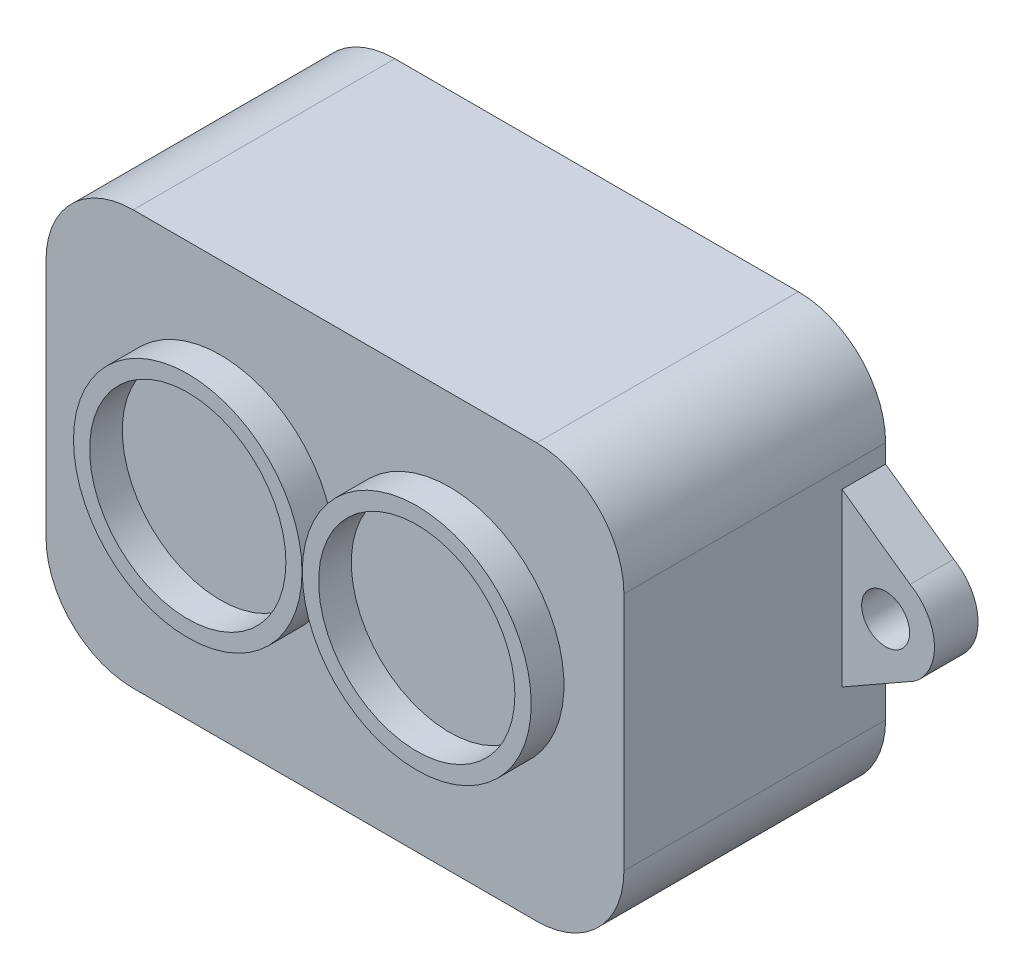
SolidWorks part; units mm, degrees
ref_plane "前视基准面" through (0, 0, 0) normal (0, 0, 1) x (1, 0, 0)
ref_plane "上视基准面" through (0, 0, 0) normal (0, 1, 0) x (1, 0, 0)
ref_plane "右视基准面" through (0, 0, 0) normal (1, 0, 0) x (0, 0, -1)
sketch "草图1" plane through (0, 0, 0) normal (0, 0, 1) x (1, 0, 0)
  line L1 (-13.25, -9.5) -> (13.25, -9.5)
  line L2 (-13.25, -9.5) -> (-13.25, 9.5)
  line L3 (-13.25, 9.5) -> (13.25, 9.5)
  line L4 (13.25, -9.5) -> (13.25, 9.5)
  line L5 (-13.25, -9.5) -> (13.25, 9.5) construction
  line L6 (-13.25, 9.5) -> (13.25, -9.5) construction
  point P0 (0, 0)
  dimension "D1" = 26.5
  dimension "D2" = 19
extrude "凸台-拉伸1" add sketch "草图1" along normal blind 12
sketch "草图2" plane through (0, 0, 12) normal (0, 0, 1) x (1, 0, 0)
  line L0 (0, 9.5) -> (0, 0.5)
  line L1 (13.25, 9.5) -> (-13.25, 9.5) construction
  line L2 (0, 0.5) -> (-5.25, 0.5)
  line L3 (0, 0.5) -> (5.25, 0.5)
  circle A0 centre (-5.25, 0.5) radius 5.25
  circle A1 centre (5.25, 0.5) radius 5.25
  circle A2 centre (-5.25, 0.5) radius 4.5
  circle A3 centre (5.25, 0.5) radius 4.5
  dimension "D3" = 5.25
  dimension "D1" = 9
  dimension "D2" = 5.25
extrude "凸台-拉伸6" add sketch "草图2" along normal blind 1.5
fillet "圆角1" radius 4 4 edges at (-13.25, 9.5, 6) (-13.25, -9.5, 6) (13.25, -9.5, 6) (13.25, 9.5, 6)
sketch "草图3" plane through (0, 0, 0) normal (0, 0, -1) x (-1, 0, 0)
  line L0 (0, 9.5) -> (0, 0.5)
  line L1 (-9.25, 9.5) -> (9.25, 9.5) construction
  line L2 (0, 0.5) -> (-15.25, 0.5)
  line L3 (-16.3734, 2.4375) -> (-16.5782, -1.3034)
  line L4 (-16.5782, -1.3034) -> (-13.25, -3.1974)
  line L5 (-13.25, -5.5) -> (-13.25, 5.5) construction
  line L6 (-16.3734, 2.4375) -> (-13.25, 4.6541)
  line L7 (-13.25, 4.6541) -> (-13.25, -3.1974)
  circle A0 centre (-15.25, 0.5) radius 1.1
  circle A1 centre (-15.25, 0.5) radius 2.2397
  dimension "D3" = 3.83
  dimension "D1" = 9
  dimension "D2" = 15.25
extrude "凸台-拉伸7" add sketch "草图3" against normal blind 2 separate body
mirror "镜向3" about plane through (0, 0, 0) normal (1, 0, 0) of "凸台-拉伸7"
sketch "草图4" plane through (0, 0, 12) normal (0, 0, 1) x (1, 0, 0)
  line L0 (0, 9.5) -> (0, 0.5)
  line L2 (9.25, 9.5) -> (-9.25, 9.5) construction
  line L3 (0, 0.5) -> (-5.25, 0.5)
  circle A0 centre (-5.25, 0.5) radius 5.24
  circle A1 centre (-5.25, 0.5) radius 4.5
  dimension "D1" = 9
  dimension "D2" = 5.25
extrude "凸台-拉伸11" add sketch "草图4" along normal blind 1.5
sketch "草图5" plane through (0, 0, 0) normal (0, 0, -1) x (-1, 0, 0)
  line L3 (9, -7.25) -> (-9, -7.25)
  line L4 (9, -7.25) -> (9, -11.75)
  line L5 (9, -11.75) -> (-9, -11.75)
  line L6 (-9, -7.25) -> (-9, -11.75)
  line L7 (9, -7.25) -> (-9, -11.75) construction
  line L8 (9, -11.75) -> (-9, -7.25) construction
  dimension "D1" = 18
  dimension "D2" = 4.5
extrude "凸台-拉伸12" add sketch "草图5" against normal blind 8.8
fillet "圆角2" radius 2 2 edges at (-9, -10.625, 8.8) (9, -10.625, 8.8)
fillet "圆角3" radius 1 2 edges at (9, -11.75, 3.4) (-9, -11.75, 3.4)
sketch "草图6" plane through (0, -11.75, 0) normal (0, -1, 0) x (1, 0, 0)
  line L0 (-5.25, 6.8) -> (-5.25, 0)
  line L1 (-5.25, 0) -> (5.25, 0)
  line L3 (8, 0) -> (-8, 0) construction
  line L6 (-5.25, 6.8) -> (5.25, 6.8)
  line L8 (5.25, 6.8) -> (5.25, 0)
  dimension "D1" = 10.5
extrude "切除-拉伸1" cut sketch "草图6" against normal blind 5
fillet "圆角4" radius 1 2 edges at (5.25, -9.25, 6.8) (-5.25, -9.25, 6.8)
